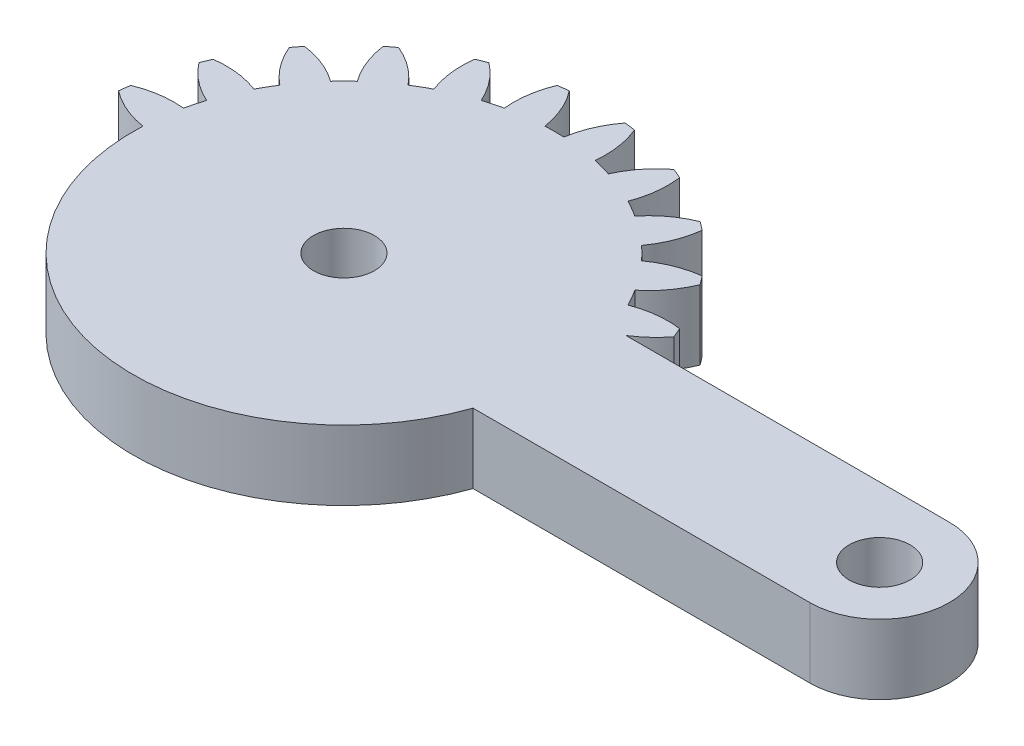
SolidWorks part; units mm, degrees
ref_plane "Front Plane" through (0, 0, 0) normal (0, 0, 1) x (1, 0, 0)
ref_plane "Top Plane" through (0, 0, 0) normal (0, 1, 0) x (1, 0, 0)
ref_plane "Right Plane" through (0, 0, 0) normal (1, 0, 0) x (0, 0, -1)
sketch "Sketch1" plane through (0, 0, 0) normal (0, 1, 0) x (1, 0, 0)
  line L0 (20.6437, 4) -> (2.0816, 4)
  line L1 (2.0816, -4) -> (20.6437, -4)
  arc A0 (2.0816, 4) -> (3.5217, 5.3071) centre (-0.7683, 8.5867) ccw
  arc A1 (3.5217, 5.3071) -> (3.2829, 5.8838) centre (-10.1063, 0) ccw
  arc A2 (3.2829, 5.8838) -> (0.6271, 5.5703) centre (2.5684, 0.5313) ccw
  arc A3 (0.6271, 5.5703) -> (0.0844, 6.5103) centre (-10.1063, 0) ccw
  arc A4 (0.0844, 6.5103) -> (1.6838, 8.6535) centre (-3.3089, 10.711) ccw
  arc A5 (1.6838, 8.6535) -> (1.3038, 9.1487) centre (-10.1063, 0) ccw
  arc A6 (1.3038, 9.1487) -> (-1.1803, 8.1585) centre (1.999, 3.7936) ccw
  arc A7 (-1.1803, 8.1585) -> (-1.9479, 8.926) centre (-10.1063, 0) ccw
  arc A8 (-1.9479, 8.926) -> (-0.9576, 11.4102) centre (-6.3127, 12.1053) ccw
  arc A9 (-0.9576, 11.4102) -> (-1.4528, 11.7901) centre (-10.1063, 0) ccw
  arc A10 (-1.4528, 11.7901) -> (-3.596, 10.1907) centre (0.6046, 6.7975) ccw
  arc A11 (-3.596, 10.1907) -> (-4.5361, 10.7334) centre (-10.1063, 0) ccw
  arc A12 (-4.5361, 10.7334) -> (-4.2225, 13.3892) centre (-9.5751, 12.6747) ccw
  arc A13 (-4.2225, 13.3892) -> (-4.7992, 13.6281) centre (-10.1063, 0) ccw
  arc A14 (-4.7992, 13.6281) -> (-6.4554, 11.5285) centre (-1.5196, 9.3381) ccw
  arc A15 (-6.4554, 11.5285) -> (-7.5039, 11.8094) centre (-10.1063, 0) ccw
  arc A16 (-7.5039, 11.8094) -> (-7.8884, 14.4558) centre (-12.8736, 12.3803) ccw
  arc A17 (-7.8884, 14.4558) -> (-8.5072, 14.5373) centre (-10.1063, 0) ccw
  arc A18 (-8.5072, 14.5373) -> (-9.5636, 12.0806) centre (-4.2291, 11.2423) ccw
  arc A19 (-9.5636, 12.0806) -> (-10.6491, 12.0806) centre (-10.1063, 0) ccw
  arc A20 (-10.6491, 12.0806) -> (-11.7054, 14.5373) centre (-15.9836, 11.2423) ccw
  arc A21 (-11.7054, 14.5373) -> (-12.3243, 14.4558) centre (-10.1063, 0) ccw
  arc A22 (-12.3243, 14.4558) -> (-12.7088, 11.8094) centre (-7.3391, 12.3803) ccw
  arc A23 (-12.7088, 11.8094) -> (-13.7573, 11.5285) centre (-10.1063, 0) ccw
  arc A24 (-13.7573, 11.5285) -> (-15.4135, 13.6281) centre (-18.6931, 9.3381) ccw
  arc A25 (-15.4135, 13.6281) -> (-15.9901, 13.3892) centre (-10.1063, 0) ccw
  arc A26 (-15.9901, 13.3892) -> (-15.6766, 10.7334) centre (-10.6376, 12.6747) ccw
  arc A27 (-15.6766, 10.7334) -> (-16.6166, 10.1907) centre (-10.1063, 0) ccw
  arc A28 (-16.6166, 10.1907) -> (-18.7599, 11.7901) centre (-20.8173, 6.7975) ccw
  arc A29 (-18.7599, 11.7901) -> (-19.255, 11.4102) centre (-10.1063, 0) ccw
  arc A30 (-19.255, 11.4102) -> (-18.2648, 8.926) centre (-13.9, 12.1053) ccw
  arc A31 (-18.2648, 8.926) -> (-19.0324, 8.1585) centre (-10.1063, 0) ccw
  arc A32 (-19.0324, 8.1585) -> (-21.5165, 9.1487) centre (-22.2117, 3.7936) ccw
  arc A33 (-21.5165, 9.1487) -> (-21.8965, 8.6535) centre (-10.1063, 0) ccw
  arc A34 (-21.8965, 8.6535) -> (-20.2971, 6.5103) centre (-16.9038, 10.711) ccw
  arc A35 (-20.2971, 6.5103) -> (-20.8398, 5.5703) centre (-10.1063, 0) ccw
  arc A36 (-20.8398, 5.5703) -> (-23.4956, 5.8838) centre (-22.7811, 0.5313) ccw
  arc A37 (-23.4956, 5.8838) -> (-23.7344, 5.3071) centre (-10.1063, 0) ccw
  arc A38 (-23.7344, 5.3071) -> (-21.6348, 3.6509) centre (-19.4444, 8.5867) ccw
  arc A39 (-21.6348, 3.6509) -> (-21.9157, 2.6025) centre (-10.1063, 0) ccw
  arc A40 (-21.9157, 2.6025) -> (-24.5622, 2.2179) centre (-22.4867, -2.7673) ccw
  arc A41 (-24.5622, 2.2179) -> (-24.6437, 1.5991) centre (-10.1063, 0) ccw
  arc A42 (-24.6437, 1.5991) -> (-22.1869, 0.5427) centre (-21.3486, 5.8773) ccw
  arc A43 (-22.1869, 0.5427) -> (-22.1869, -0.5427) centre (-10.1063, 0) ccw
  arc A44 (-22.1869, -0.5427) -> (-24.6437, -1.5991) centre (-21.3486, -5.8773) ccw
  arc A45 (-24.6437, -1.5991) -> (-24.5622, -2.2179) centre (-10.1063, 0) ccw
  arc A46 (-24.5622, -2.2179) -> (-21.9157, -2.6025) centre (-22.4867, 2.7673) ccw
  arc A47 (-21.9157, -2.6025) -> (-21.6348, -3.6509) centre (-10.1063, 0) ccw
  arc A48 (-21.6348, -3.6509) -> (-23.7344, -5.3071) centre (-19.4444, -8.5867) ccw
  arc A49 (-23.7344, -5.3071) -> (-23.4956, -5.8838) centre (-10.1063, 0) ccw
  arc A50 (-23.4956, -5.8838) -> (-20.8398, -5.5703) centre (-22.7811, -0.5313) ccw
  arc A51 (-20.8398, -5.5703) -> (-20.2971, -6.5103) centre (-10.1063, 0) ccw
  arc A52 (-20.2971, -6.5103) -> (-21.8965, -8.6535) centre (-16.9038, -10.711) ccw
  arc A53 (-21.8965, -8.6535) -> (-21.5165, -9.1487) centre (-10.1063, 0) ccw
  arc A54 (-21.5165, -9.1487) -> (-19.0324, -8.1585) centre (-22.2117, -3.7936) ccw
  arc A55 (-19.0324, -8.1585) -> (-18.2648, -8.926) centre (-10.1063, 0) ccw
  arc A56 (-18.2648, -8.926) -> (-19.255, -11.4102) centre (-13.9, -12.1053) ccw
  arc A57 (-19.255, -11.4102) -> (-18.7599, -11.7901) centre (-10.1063, 0) ccw
  arc A58 (-18.7599, -11.7901) -> (-16.6166, -10.1907) centre (-20.8173, -6.7975) ccw
  arc A59 (-16.6166, -10.1907) -> (-15.6766, -10.7334) centre (-10.1063, 0) ccw
  arc A60 (-15.6766, -10.7334) -> (-15.9901, -13.3892) centre (-10.6376, -12.6747) ccw
  arc A61 (-15.9901, -13.3892) -> (-15.4135, -13.6281) centre (-10.1063, 0) ccw
  arc A62 (-15.4135, -13.6281) -> (-13.7573, -11.5285) centre (-18.6931, -9.3381) ccw
  arc A63 (-13.7573, -11.5285) -> (-12.7088, -11.8094) centre (-10.1063, 0) ccw
  arc A64 (-12.7088, -11.8094) -> (-12.3243, -14.4558) centre (-7.3391, -12.3803) ccw
  arc A65 (-12.3243, -14.4558) -> (-11.7054, -14.5373) centre (-10.1063, 0) ccw
  arc A66 (-11.7054, -14.5373) -> (-10.6491, -12.0806) centre (-15.9836, -11.2423) ccw
  arc A67 (-10.6491, -12.0806) -> (-9.5636, -12.0806) centre (-10.1063, 0) ccw
  arc A68 (-9.5636, -12.0806) -> (-8.5072, -14.5373) centre (-4.2291, -11.2423) ccw
  arc A69 (-8.5072, -14.5373) -> (-7.8884, -14.4558) centre (-10.1063, 0) ccw
  arc A70 (-7.8884, -14.4558) -> (-7.5039, -11.8094) centre (-12.8736, -12.3803) ccw
  arc A71 (-7.5039, -11.8094) -> (-6.4554, -11.5285) centre (-10.1063, 0) ccw
  arc A72 (-6.4554, -11.5285) -> (-4.7992, -13.6281) centre (-1.5196, -9.3381) ccw
  arc A73 (-4.7992, -13.6281) -> (-4.2225, -13.3892) centre (-10.1063, 0) ccw
  arc A74 (-4.2225, -13.3892) -> (-4.5361, -10.7334) centre (-9.5751, -12.6747) ccw
  arc A75 (-4.5361, -10.7334) -> (-3.596, -10.1907) centre (-10.1063, 0) ccw
  arc A76 (-3.596, -10.1907) -> (-1.4528, -11.7901) centre (0.6046, -6.7975) ccw
  arc A77 (-1.4528, -11.7901) -> (-0.9576, -11.4102) centre (-10.1063, 0) ccw
  arc A78 (-0.9576, -11.4102) -> (-1.9479, -8.926) centre (-6.3127, -12.1053) ccw
  arc A79 (-1.9479, -8.926) -> (-1.1803, -8.1585) centre (-10.1063, 0) ccw
  arc A80 (-1.1803, -8.1585) -> (1.3038, -9.1487) centre (1.999, -3.7936) ccw
  arc A81 (1.3038, -9.1487) -> (1.6838, -8.6535) centre (-10.1063, 0) ccw
  arc A82 (1.6838, -8.6535) -> (0.0844, -6.5103) centre (-3.3089, -10.711) ccw
  arc A83 (0.0844, -6.5103) -> (0.6271, -5.5703) centre (-10.1063, 0) ccw
  arc A84 (0.6271, -5.5703) -> (3.2829, -5.8838) centre (2.5684, -0.5313) ccw
  arc A85 (3.2829, -5.8838) -> (3.5217, -5.3071) centre (-10.1063, 0) ccw
  arc A86 (3.5217, -5.3071) -> (2.0816, -4) centre (-0.7683, -8.5867) ccw
  arc A87 (20.6437, -4) -> (20.6437, 4) centre (20.6437, 0) ccw
  circle A88 centre (-10.1063, 0) radius 1.75
  circle A89 centre (20.6437, 0) radius 1.75
  dimension "D1" = 3.5
  dimension "D2" = 3.5
extrude "Boss-Extrude1" add sketch "Sketch1" along normal blind 4
sketch "Sketch2" plane through (0, 4, 0) normal (0, 1, 0) x (1, 0, 0)
  line L0 (2.0816, -4) -> (1.3057, -4)
  line L2 (20.6437, 4) -> (2.0816, 4)
  line L3 (2.0816, -4) -> (20.6437, -4)
  line L4 (20.6437, 4) -> (2.0816, 4)
  line L5 (2.0816, -4) -> (20.6437, -4)
  circle A0 centre (-10.1063, 0) radius 12.0927
  arc A88 (20.6437, -4) -> (20.6437, 4) centre (20.6437, 0) ccw
  arc A89 (2.0816, 4) -> (3.5217, 5.3071) centre (-0.7683, 8.5867) ccw
  arc A90 (3.5217, 5.3071) -> (3.2829, 5.8838) centre (-10.1063, 0) ccw
  arc A91 (3.2829, 5.8838) -> (0.6271, 5.5703) centre (2.5684, 0.5313) ccw
  arc A92 (0.6271, 5.5703) -> (0.0844, 6.5103) centre (-10.1063, 0) ccw
  arc A93 (0.0844, 6.5103) -> (1.6838, 8.6535) centre (-3.3089, 10.711) ccw
  arc A94 (1.6838, 8.6535) -> (1.3038, 9.1487) centre (-10.1063, 0) ccw
  arc A95 (1.3038, 9.1487) -> (-1.1803, 8.1585) centre (1.999, 3.7936) ccw
  arc A96 (-1.1803, 8.1585) -> (-1.9479, 8.926) centre (-10.1063, 0) ccw
  arc A97 (-1.9479, 8.926) -> (-0.9576, 11.4102) centre (-6.3127, 12.1053) ccw
  arc A98 (-0.9576, 11.4102) -> (-1.4528, 11.7901) centre (-10.1063, 0) ccw
  arc A99 (-1.4528, 11.7901) -> (-3.596, 10.1907) centre (0.6046, 6.7975) ccw
  arc A100 (-3.596, 10.1907) -> (-4.5361, 10.7334) centre (-10.1063, 0) ccw
  arc A101 (-4.5361, 10.7334) -> (-4.2225, 13.3892) centre (-9.5751, 12.6747) ccw
  arc A102 (-4.2225, 13.3892) -> (-4.7992, 13.6281) centre (-10.1063, 0) ccw
  arc A103 (-4.7992, 13.6281) -> (-6.4554, 11.5285) centre (-1.5196, 9.3381) ccw
  arc A104 (-6.4554, 11.5285) -> (-7.5039, 11.8094) centre (-10.1063, 0) ccw
  arc A105 (-7.5039, 11.8094) -> (-7.8884, 14.4558) centre (-12.8736, 12.3803) ccw
  arc A106 (-7.8884, 14.4558) -> (-8.5072, 14.5373) centre (-10.1063, 0) ccw
  arc A107 (-8.5072, 14.5373) -> (-9.5636, 12.0806) centre (-4.2291, 11.2423) ccw
  arc A108 (-9.5636, 12.0806) -> (-10.6491, 12.0806) centre (-10.1063, 0) ccw
  arc A109 (-10.6491, 12.0806) -> (-11.7054, 14.5373) centre (-15.9836, 11.2423) ccw
  arc A110 (-11.7054, 14.5373) -> (-12.3243, 14.4558) centre (-10.1063, 0) ccw
  arc A111 (-12.3243, 14.4558) -> (-12.7088, 11.8094) centre (-7.3391, 12.3803) ccw
  arc A112 (-12.7088, 11.8094) -> (-13.7573, 11.5285) centre (-10.1063, 0) ccw
  arc A113 (-13.7573, 11.5285) -> (-15.4135, 13.6281) centre (-18.6931, 9.3381) ccw
  arc A114 (-15.4135, 13.6281) -> (-15.9901, 13.3892) centre (-10.1063, 0) ccw
  arc A115 (-15.9901, 13.3892) -> (-15.6766, 10.7334) centre (-10.6376, 12.6747) ccw
  arc A116 (-15.6766, 10.7334) -> (-16.6166, 10.1907) centre (-10.1063, 0) ccw
  arc A117 (-16.6166, 10.1907) -> (-18.7599, 11.7901) centre (-20.8173, 6.7975) ccw
  arc A118 (-18.7599, 11.7901) -> (-19.255, 11.4102) centre (-10.1063, 0) ccw
  arc A119 (-19.255, 11.4102) -> (-18.2648, 8.926) centre (-13.9, 12.1053) ccw
  arc A120 (-18.2648, 8.926) -> (-19.0324, 8.1585) centre (-10.1063, 0) ccw
  arc A121 (-19.0324, 8.1585) -> (-21.5165, 9.1487) centre (-22.2117, 3.7936) ccw
  arc A122 (-21.5165, 9.1487) -> (-21.8965, 8.6535) centre (-10.1063, 0) ccw
  arc A123 (-21.8965, 8.6535) -> (-20.2971, 6.5103) centre (-16.9038, 10.711) ccw
  arc A124 (-20.2971, 6.5103) -> (-20.8398, 5.5703) centre (-10.1063, 0) ccw
  arc A125 (-20.8398, 5.5703) -> (-23.4956, 5.8838) centre (-22.7811, 0.5313) ccw
  arc A126 (-23.4956, 5.8838) -> (-23.7344, 5.3071) centre (-10.1063, 0) ccw
  arc A127 (-23.7344, 5.3071) -> (-21.6348, 3.6509) centre (-19.4444, 8.5867) ccw
  arc A128 (-21.6348, 3.6509) -> (-21.9157, 2.6025) centre (-10.1063, 0) ccw
  arc A129 (-21.9157, 2.6025) -> (-24.5622, 2.2179) centre (-22.4867, -2.7673) ccw
  arc A130 (-24.5622, 2.2179) -> (-24.6437, 1.5991) centre (-10.1063, 0) ccw
  arc A131 (-24.6437, 1.5991) -> (-22.1869, 0.5427) centre (-21.3486, 5.8773) ccw
  arc A132 (-22.1869, 0.5427) -> (-22.1869, -0.5427) centre (-10.1063, 0) ccw
  arc A133 (-22.1869, -0.5427) -> (-24.6437, -1.5991) centre (-21.3486, -5.8773) ccw
  arc A134 (-24.6437, -1.5991) -> (-24.5622, -2.2179) centre (-10.1063, 0) ccw
  arc A135 (-24.5622, -2.2179) -> (-21.9157, -2.6025) centre (-22.4867, 2.7673) ccw
  arc A136 (-21.9157, -2.6025) -> (-21.6348, -3.6509) centre (-10.1063, 0) ccw
  arc A137 (-21.6348, -3.6509) -> (-23.7344, -5.3071) centre (-19.4444, -8.5867) ccw
  arc A138 (-23.7344, -5.3071) -> (-23.4956, -5.8838) centre (-10.1063, 0) ccw
  arc A139 (-23.4956, -5.8838) -> (-20.8398, -5.5703) centre (-22.7811, -0.5313) ccw
  arc A140 (-20.8398, -5.5703) -> (-20.2971, -6.5103) centre (-10.1063, 0) ccw
  arc A141 (-20.2971, -6.5103) -> (-21.8965, -8.6535) centre (-16.9038, -10.711) ccw
  arc A142 (-21.8965, -8.6535) -> (-21.5165, -9.1487) centre (-10.1063, 0) ccw
  arc A143 (-21.5165, -9.1487) -> (-19.0324, -8.1585) centre (-22.2117, -3.7936) ccw
  arc A144 (-19.0324, -8.1585) -> (-18.2648, -8.926) centre (-10.1063, 0) ccw
  arc A145 (-18.2648, -8.926) -> (-19.255, -11.4102) centre (-13.9, -12.1053) ccw
  arc A146 (-19.255, -11.4102) -> (-18.7599, -11.7901) centre (-10.1063, 0) ccw
  arc A147 (-18.7599, -11.7901) -> (-16.6166, -10.1907) centre (-20.8173, -6.7975) ccw
  arc A148 (-16.6166, -10.1907) -> (-15.6766, -10.7334) centre (-10.1063, 0) ccw
  arc A149 (-15.6766, -10.7334) -> (-15.9901, -13.3892) centre (-10.6376, -12.6747) ccw
  arc A150 (-15.9901, -13.3892) -> (-15.4135, -13.6281) centre (-10.1063, 0) ccw
  arc A151 (-15.4135, -13.6281) -> (-13.7573, -11.5285) centre (-18.6931, -9.3381) ccw
  arc A152 (-13.7573, -11.5285) -> (-12.7088, -11.8094) centre (-10.1063, 0) ccw
  arc A153 (-12.7088, -11.8094) -> (-12.3243, -14.4558) centre (-7.3391, -12.3803) ccw
  arc A154 (-12.3243, -14.4558) -> (-11.7054, -14.5373) centre (-10.1063, 0) ccw
  arc A155 (-11.7054, -14.5373) -> (-10.6491, -12.0806) centre (-15.9836, -11.2423) ccw
  arc A156 (-10.6491, -12.0806) -> (-9.5636, -12.0806) centre (-10.1063, 0) ccw
  arc A157 (-9.5636, -12.0806) -> (-8.5072, -14.5373) centre (-4.2291, -11.2423) ccw
  arc A158 (-8.5072, -14.5373) -> (-7.8884, -14.4558) centre (-10.1063, 0) ccw
  arc A159 (-7.8884, -14.4558) -> (-7.5039, -11.8094) centre (-12.8736, -12.3803) ccw
  arc A160 (-7.5039, -11.8094) -> (-6.4554, -11.5285) centre (-10.1063, 0) ccw
  arc A161 (-6.4554, -11.5285) -> (-4.7992, -13.6281) centre (-1.5196, -9.3381) ccw
  arc A162 (-4.7992, -13.6281) -> (-4.2225, -13.3892) centre (-10.1063, 0) ccw
  arc A163 (-4.2225, -13.3892) -> (-4.5361, -10.7334) centre (-9.5751, -12.6747) ccw
  arc A164 (-4.5361, -10.7334) -> (-3.596, -10.1907) centre (-10.1063, 0) ccw
  arc A165 (-3.596, -10.1907) -> (-1.4528, -11.7901) centre (0.6046, -6.7975) ccw
  arc A166 (-1.4528, -11.7901) -> (-0.9576, -11.4102) centre (-10.1063, 0) ccw
  arc A167 (-0.9576, -11.4102) -> (-1.9479, -8.926) centre (-6.3127, -12.1053) ccw
  arc A168 (-1.9479, -8.926) -> (-1.1803, -8.1585) centre (-10.1063, 0) ccw
  arc A169 (-1.1803, -8.1585) -> (1.3038, -9.1487) centre (1.999, -3.7936) ccw
  arc A170 (1.3038, -9.1487) -> (1.6838, -8.6535) centre (-10.1063, 0) ccw
  arc A171 (1.6838, -8.6535) -> (0.0844, -6.5103) centre (-3.3089, -10.711) ccw
  arc A172 (0.0844, -6.5103) -> (0.6271, -5.5703) centre (-10.1063, 0) ccw
  arc A173 (0.6271, -5.5703) -> (3.2829, -5.8838) centre (2.5684, -0.5313) ccw
  arc A174 (3.2829, -5.8838) -> (3.5217, -5.3071) centre (-10.1063, 0) ccw
  arc A175 (3.5217, -5.3071) -> (2.0816, -4) centre (-0.7683, -8.5867) ccw
  arc A176 (20.6437, -4) -> (20.6437, 4) centre (20.6437, 0) ccw
  arc A177 (2.0816, 4) -> (3.5217, 5.3071) centre (-0.7683, 8.5867) ccw
  arc A178 (3.5217, 5.3071) -> (3.2829, 5.8838) centre (-10.1063, 0) ccw
  arc A179 (3.2829, 5.8838) -> (0.6271, 5.5703) centre (2.5684, 0.5313) ccw
  arc A180 (0.6271, 5.5703) -> (0.0844, 6.5103) centre (-10.1063, 0) ccw
  arc A181 (0.0844, 6.5103) -> (1.6838, 8.6535) centre (-3.3089, 10.711) ccw
  arc A182 (1.6838, 8.6535) -> (1.3038, 9.1487) centre (-10.1063, 0) ccw
  arc A183 (1.3038, 9.1487) -> (-1.1803, 8.1585) centre (1.999, 3.7936) ccw
  arc A184 (-1.1803, 8.1585) -> (-1.9479, 8.926) centre (-10.1063, 0) ccw
  arc A185 (-1.9479, 8.926) -> (-0.9576, 11.4102) centre (-6.3127, 12.1053) ccw
  arc A186 (-0.9576, 11.4102) -> (-1.4528, 11.7901) centre (-10.1063, 0) ccw
  arc A187 (-1.4528, 11.7901) -> (-3.596, 10.1907) centre (0.6046, 6.7975) ccw
  arc A188 (-3.596, 10.1907) -> (-4.5361, 10.7334) centre (-10.1063, 0) ccw
  arc A189 (-4.5361, 10.7334) -> (-4.2225, 13.3892) centre (-9.5751, 12.6747) ccw
  arc A190 (-4.2225, 13.3892) -> (-4.7992, 13.6281) centre (-10.1063, 0) ccw
  arc A191 (-4.7992, 13.6281) -> (-6.4554, 11.5285) centre (-1.5196, 9.3381) ccw
  arc A192 (-6.4554, 11.5285) -> (-7.5039, 11.8094) centre (-10.1063, 0) ccw
  arc A193 (-7.5039, 11.8094) -> (-7.8884, 14.4558) centre (-12.8736, 12.3803) ccw
  arc A194 (-7.8884, 14.4558) -> (-8.5072, 14.5373) centre (-10.1063, 0) ccw
  arc A195 (-8.5072, 14.5373) -> (-9.5636, 12.0806) centre (-4.2291, 11.2423) ccw
  arc A196 (-9.5636, 12.0806) -> (-10.6491, 12.0806) centre (-10.1063, 0) ccw
  arc A197 (-10.6491, 12.0806) -> (-11.7054, 14.5373) centre (-15.9836, 11.2423) ccw
  arc A198 (-11.7054, 14.5373) -> (-12.3243, 14.4558) centre (-10.1063, 0) ccw
  arc A199 (-12.3243, 14.4558) -> (-12.7088, 11.8094) centre (-7.3391, 12.3803) ccw
  arc A200 (-12.7088, 11.8094) -> (-13.7573, 11.5285) centre (-10.1063, 0) ccw
  arc A201 (-13.7573, 11.5285) -> (-15.4135, 13.6281) centre (-18.6931, 9.3381) ccw
  arc A202 (-15.4135, 13.6281) -> (-15.9901, 13.3892) centre (-10.1063, 0) ccw
  arc A203 (-15.9901, 13.3892) -> (-15.6766, 10.7334) centre (-10.6376, 12.6747) ccw
  arc A204 (-15.6766, 10.7334) -> (-16.6166, 10.1907) centre (-10.1063, 0) ccw
  arc A205 (-16.6166, 10.1907) -> (-18.7599, 11.7901) centre (-20.8173, 6.7975) ccw
  arc A206 (-18.7599, 11.7901) -> (-19.255, 11.4102) centre (-10.1063, 0) ccw
  arc A207 (-19.255, 11.4102) -> (-18.2648, 8.926) centre (-13.9, 12.1053) ccw
  arc A208 (-18.2648, 8.926) -> (-19.0324, 8.1585) centre (-10.1063, 0) ccw
  arc A209 (-19.0324, 8.1585) -> (-21.5165, 9.1487) centre (-22.2117, 3.7936) ccw
  arc A210 (-21.5165, 9.1487) -> (-21.8965, 8.6535) centre (-10.1063, 0) ccw
  arc A211 (-21.8965, 8.6535) -> (-20.2971, 6.5103) centre (-16.9038, 10.711) ccw
  arc A212 (-20.2971, 6.5103) -> (-20.8398, 5.5703) centre (-10.1063, 0) ccw
  arc A213 (-20.8398, 5.5703) -> (-23.4956, 5.8838) centre (-22.7811, 0.5313) ccw
  arc A214 (-23.4956, 5.8838) -> (-23.7344, 5.3071) centre (-10.1063, 0) ccw
  arc A215 (-23.7344, 5.3071) -> (-21.6348, 3.6509) centre (-19.4444, 8.5867) ccw
  arc A216 (-21.6348, 3.6509) -> (-21.9157, 2.6025) centre (-10.1063, 0) ccw
  arc A217 (-21.9157, 2.6025) -> (-24.5622, 2.2179) centre (-22.4867, -2.7673) ccw
  arc A218 (-24.5622, 2.2179) -> (-24.6437, 1.5991) centre (-10.1063, 0) ccw
  arc A219 (-24.6437, 1.5991) -> (-22.1869, 0.5427) centre (-21.3486, 5.8773) ccw
  arc A220 (-22.1869, 0.5427) -> (-22.1869, -0.5427) centre (-10.1063, 0) ccw
  arc A221 (-22.1869, -0.5427) -> (-24.6437, -1.5991) centre (-21.3486, -5.8773) ccw
  arc A222 (-24.6437, -1.5991) -> (-24.5622, -2.2179) centre (-10.1063, 0) ccw
  arc A223 (-24.5622, -2.2179) -> (-21.9157, -2.6025) centre (-22.4867, 2.7673) ccw
  arc A224 (-21.9157, -2.6025) -> (-21.6348, -3.6509) centre (-10.1063, 0) ccw
  arc A225 (-21.6348, -3.6509) -> (-23.7344, -5.3071) centre (-19.4444, -8.5867) ccw
  arc A226 (-23.7344, -5.3071) -> (-23.4956, -5.8838) centre (-10.1063, 0) ccw
  arc A227 (-23.4956, -5.8838) -> (-20.8398, -5.5703) centre (-22.7811, -0.5313) ccw
  arc A228 (-20.8398, -5.5703) -> (-20.2971, -6.5103) centre (-10.1063, 0) ccw
  arc A229 (-20.2971, -6.5103) -> (-21.8965, -8.6535) centre (-16.9038, -10.711) ccw
  arc A230 (-21.8965, -8.6535) -> (-21.5165, -9.1487) centre (-10.1063, 0) ccw
  arc A231 (-21.5165, -9.1487) -> (-19.0324, -8.1585) centre (-22.2117, -3.7936) ccw
  arc A232 (-19.0324, -8.1585) -> (-18.2648, -8.926) centre (-10.1063, 0) ccw
  arc A233 (-18.2648, -8.926) -> (-19.255, -11.4102) centre (-13.9, -12.1053) ccw
  arc A234 (-19.255, -11.4102) -> (-18.7599, -11.7901) centre (-10.1063, 0) ccw
  arc A235 (-18.7599, -11.7901) -> (-16.6166, -10.1907) centre (-20.8173, -6.7975) ccw
  arc A236 (-16.6166, -10.1907) -> (-15.6766, -10.7334) centre (-10.1063, 0) ccw
  arc A237 (-15.6766, -10.7334) -> (-15.9901, -13.3892) centre (-10.6376, -12.6747) ccw
  arc A238 (-15.9901, -13.3892) -> (-15.4135, -13.6281) centre (-10.1063, 0) ccw
  arc A239 (-15.4135, -13.6281) -> (-13.7573, -11.5285) centre (-18.6931, -9.3381) ccw
  arc A240 (-13.7573, -11.5285) -> (-12.7088, -11.8094) centre (-10.1063, 0) ccw
  arc A241 (-12.7088, -11.8094) -> (-12.3243, -14.4558) centre (-7.3391, -12.3803) ccw
  arc A242 (-12.3243, -14.4558) -> (-11.7054, -14.5373) centre (-10.1063, 0) ccw
  arc A243 (-11.7054, -14.5373) -> (-10.6491, -12.0806) centre (-15.9836, -11.2423) ccw
  arc A244 (-10.6491, -12.0806) -> (-9.5636, -12.0806) centre (-10.1063, 0) ccw
  arc A245 (-9.5636, -12.0806) -> (-8.5072, -14.5373) centre (-4.2291, -11.2423) ccw
  arc A246 (-8.5072, -14.5373) -> (-7.8884, -14.4558) centre (-10.1063, 0) ccw
  arc A247 (-7.8884, -14.4558) -> (-7.5039, -11.8094) centre (-12.8736, -12.3803) ccw
  arc A248 (-7.5039, -11.8094) -> (-6.4554, -11.5285) centre (-10.1063, 0) ccw
  arc A249 (-6.4554, -11.5285) -> (-4.7992, -13.6281) centre (-1.5196, -9.3381) ccw
  arc A250 (-4.7992, -13.6281) -> (-4.2225, -13.3892) centre (-10.1063, 0) ccw
  arc A251 (-4.2225, -13.3892) -> (-4.5361, -10.7334) centre (-9.5751, -12.6747) ccw
  arc A252 (-4.5361, -10.7334) -> (-3.596, -10.1907) centre (-10.1063, 0) ccw
  arc A253 (-3.596, -10.1907) -> (-1.4528, -11.7901) centre (0.6046, -6.7975) ccw
  arc A254 (-1.4528, -11.7901) -> (-0.9576, -11.4102) centre (-10.1063, 0) ccw
  arc A255 (-0.9576, -11.4102) -> (-1.9479, -8.926) centre (-6.3127, -12.1053) ccw
  arc A256 (-1.9479, -8.926) -> (-1.1803, -8.1585) centre (-10.1063, 0) ccw
  arc A257 (-1.1803, -8.1585) -> (1.3038, -9.1487) centre (1.999, -3.7936) ccw
  arc A258 (1.3038, -9.1487) -> (1.6838, -8.6535) centre (-10.1063, 0) ccw
  arc A259 (1.6838, -8.6535) -> (0.0844, -6.5103) centre (-3.3089, -10.711) ccw
  arc A260 (0.0844, -6.5103) -> (0.6271, -5.5703) centre (-10.1063, 0) ccw
  arc A261 (0.6271, -5.5703) -> (3.2829, -5.8838) centre (2.5684, -0.5313) ccw
  arc A262 (3.2829, -5.8838) -> (3.5217, -5.3071) centre (-10.1063, 0) ccw
  arc A263 (3.5217, -5.3071) -> (2.0816, -4) centre (-0.7683, -8.5867) ccw
  dimension "D1" = 0
extrude "Cut-Extrude1" cut sketch "Sketch2" against normal blind 10 contours A222 A223 A0 A221 | A226 A227 A0 A225 | A230 A231 A0 A229 | A234 A235 A0 A233 | A238 A239 A0 A237 | A242 A243 A0 A241 | A246 A247 A0 A245 | A250 A251 A0 A249 | A254 A255 A0 A253 | A258 A259 A0 A257 | A262 A263 L0 A0 A261 region at (2.066, 4, 5.0775) region at (0.3325, 4, 8.01) region at (-2.0963, 4, 10.4389) region at (-5.071, 4, 12.1563) region at (-8.3889, 4, 13.0454) region at (-11.8238, 4, 13.0454) region at (-15.1417, 4, 12.1563) region at (-18.1164, 4, 10.4389) region at (-20.5452, 4, 8.01) region at (-22.2627, 4, 5.0353) region at (-23.1517, 4, 1.7175)
